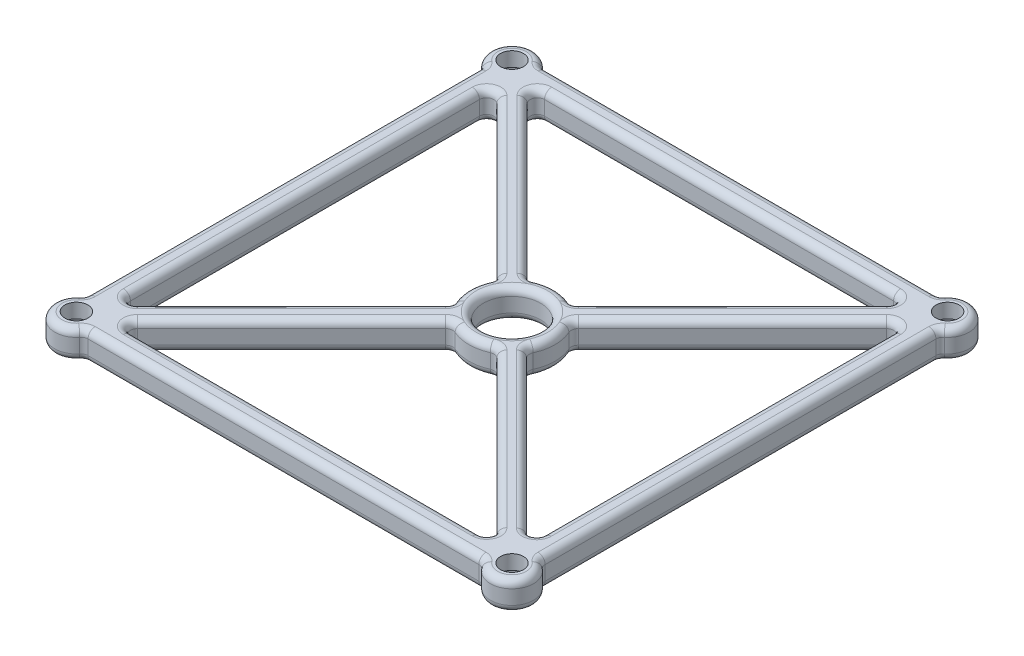
SolidWorks part; units mm, degrees
ref_plane "Front" through (0, 0, 0) normal (0, 0, 1) x (1, 0, 0)
ref_plane "Top" through (0, 0, 0) normal (0, 1, 0) x (1, 0, 0)
ref_plane "Right" through (0, 0, 0) normal (1, 0, 0) x (0, 0, -1)
sketch "Sketch1" plane through (0, 0, 0) normal (0, 1, 0) x (1, 0, 0)
  line L1 (-14.425, 13.3643) -> (-2.5843, 1.5236)
  line L3 (-14.425, 13.3643) -> (-14.425, -13.3643)
  line L9 (-2.5843, -1.5236) -> (-14.425, -13.3643)
  line L10 (1.5236, 2.5843) -> (13.3643, 14.425)
  line L11 (-1.5236, 2.5843) -> (-13.3643, 14.425)
  line L12 (-13.3643, 14.425) -> (13.3643, 14.425)
  line L13 (-13.3643, -14.425) -> (13.3643, -14.425)
  line L14 (1.5236, -2.5843) -> (13.3643, -14.425)
  line L15 (-1.5236, -2.5843) -> (-13.3643, -14.425)
  line L16 (2.5843, 1.5236) -> (14.425, 13.3643)
  line L17 (14.425, 13.3643) -> (14.425, -13.4112)
  line L18 (2.5667, -1.553) -> (14.425, -13.4112)
  line L21 (15.925, 13.876) -> (15.925, -13.876)
  line L24 (13.876, -15.925) -> (-13.876, -15.925)
  line L25 (-15.925, -13.876) -> (-15.925, 13.876)
  line L26 (-13.876, 15.925) -> (13.876, 15.925)
  arc A10 (-15.925, -13.876) -> (-13.876, -15.925) centre (-15.175, -15.175) ccw
  arc A11 (13.876, -15.925) -> (15.925, -13.876) centre (15.175, -15.175) ccw
  arc A12 (-15.925, 13.876) -> (-13.876, 15.925) centre (-15.175, 15.175) cw
  arc A13 (15.925, 13.876) -> (13.876, 15.925) centre (15.175, 15.175) ccw
  arc A14 (1.5236, 2.5843) -> (-1.5236, 2.5843) centre (0, 0) ccw
  arc A15 (2.5843, 1.5236) -> (2.5667, -1.553) centre (0, 0) cw
  arc A16 (-1.5236, -2.5843) -> (1.5236, -2.5843) centre (0, 0) ccw
  arc A17 (-2.5843, 1.5236) -> (-2.5843, -1.5236) centre (0, 0) ccw
extrude "Boss-Extrude1" add sketch "Sketch1" along normal blind 2
sketch "Sketch2" plane through (0, 2, 0) normal (0, 1, 0) x (1, 0, 0)
  circle A0 centre (0, 0) radius 2
extrude "Cut-Extrude1" cut sketch "Sketch2" against normal blind 2
sketch "Sketch3" plane through (0, 2, 0) normal (0, 1, 0) x (1, 0, 0)
  circle A0 centre (15.175, 15.175) radius 0.8
  circle A1 centre (15.175, -15.175) radius 0.8
  circle A2 centre (-15.175, 15.175) radius 0.8
  circle A3 centre (-15.175, -15.175) radius 0.8
extrude "Cut-Extrude2" cut sketch "Sketch3" against normal blind 2
fillet "Fillet3" radius 0.5 48 edges at (14.425, 2, 0.0235) (14.425, 0, 0.0235) (8.5046, 2, -7.444) (14.425, 1, -13.3643) (8.5046, 0, -7.444) (14.425, 1, 13.4112) (8.4959, 2, 7.4821) (8.4959, 0, 7.4821) (2.5667, 1, 1.553) (3, 2, 0.0171) (2.5843, 1, -1.5236) (3, 0, 0.0171) (0, 2, 14.425) (0, 0, 14.425) (7.444, 2, 8.5046) (13.3643, 1, 14.425) (7.444, 0, 8.5046) (0, 2, 3) (1.5236, 1, 2.5843) (0, 0, 3) (-13.3643, 1, 14.425) (-7.444, 2, 8.5046) (-1.5236, 1, 2.5843) (-7.444, 0, 8.5046) (-8.5046, 2, 7.444) (-8.5046, 0, 7.444) (-3, 2, 0) (-2.5843, 1, 1.5236) (-3, 0, 0) (-14.425, 1, 13.3643) (-14.425, 2, 0) (-14.425, 0, 0) (-14.425, 1, -13.3643) (-8.5046, 2, -7.444) (-2.5843, 1, -1.5236) (-8.5046, 0, -7.444) (0, 2, -3) (0, 0, -3) (7.444, 2, -8.5046) (1.5236, 1, -2.5843) (7.444, 0, -8.5046) (0, 2, -14.425) (13.3643, 1, -14.425) (0, 0, -14.425) (-1.5236, 1, -2.5843) (-7.444, 2, -8.5046) (-13.3643, 1, -14.425) (-7.444, 0, -8.5046)
fillet "Fillet4" radius 0.5 2 edges at (0, 2, 2) (0, 0, 2)
fillet "Fillet5" radius 0.5 24 edges at (16.2357, 2, -16.2357) (16.2357, 0, -16.2357) (16.2357, 2, 16.2357) (16.2357, 0, 16.2357) (-16.2357, 2, 16.2357) (-16.2357, 0, 16.2357) (-16.2357, 2, -16.2357) (-16.2357, 0, -16.2357) (-15.925, 1, -13.876) (-15.925, 2, 0) (-15.925, 1, 13.876) (-15.925, 0, 0) (-13.876, 1, 15.925) (0, 2, 15.925) (13.876, 1, 15.925) (0, 0, 15.925) (15.925, 1, 13.876) (15.925, 2, 0) (15.925, 1, -13.876) (15.925, 0, 0) (13.876, 1, -15.925) (0, 2, -15.925) (-13.876, 1, -15.925) (0, 0, -15.925)
sketch "Sketch4" plane through (0, 0, 0) normal (0, -1, 0) x (1, 0, 0)
  circle A0 centre (-15.175, 15.175) radius 1.2
  circle A1 centre (15.175, 15.175) radius 1.2
  circle A2 centre (-15.175, -15.175) radius 1.2
  circle A3 centre (15.175, -15.175) radius 1.2
extrude "Cut-Extrude3" cut sketch "Sketch4" against normal blind 1
fillet "Fillet6" radius 0.1 4 edges at (-16.0235, 0.0417, -16.0235) (-15.6664, 0.0121, -14.0802) (-14.3265, 0, -14.3265)
fillet "Fillet7" radius 0.1 4 edges at (-14.0802, 0.0121, 15.6664) (-14.3265, 0, 14.3265) (-16.0235, 0.0417, 16.0235)
fillet "Fillet8" radius 0.1 4 edges at (15.6664, 0.0121, 14.0802) (16.0235, 0.0417, 16.0235) (14.3265, 0, 14.3265)
fillet "Fillet9" radius 0.1 4 edges at (16.0235, 0.0417, -16.0235) (14.0802, 0.0121, -15.6664) (14.3265, 0, -14.3265)
